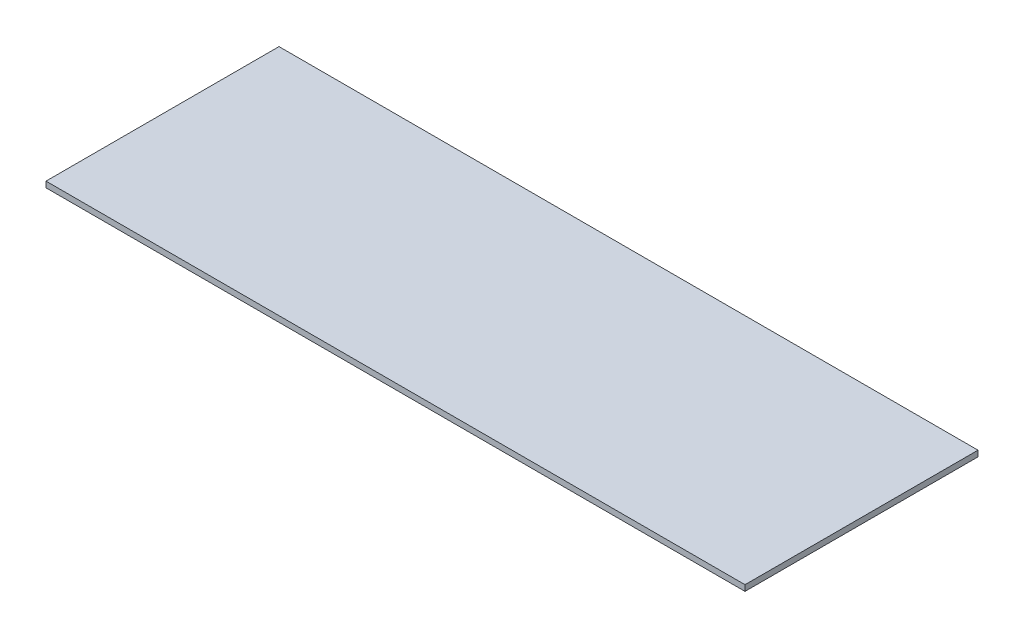
SolidWorks part; units mm, degrees
ref_plane "Front Plane" through (0, 0, 0) normal (0, 0, 1) x (1, 0, 0)
ref_plane "Top Plane" through (0, 0, 0) normal (0, 1, 0) x (1, 0, 0)
ref_plane "Right Plane" through (0, 0, 0) normal (1, 0, 0) x (0, 0, -1)
sketch "Sketch1" plane through (0, 0, 0) normal (0, 1, 0) x (1, 0, 0)
  line L1 (-73.2022, 369.585) -> (1126.7978, 369.585)
  line L2 (-73.2022, 369.585) -> (-73.2022, -30.415)
  line L3 (-73.2022, -30.415) -> (1126.7978, -30.415)
  line L4 (1126.7978, 369.585) -> (1126.7978, -30.415)
extrude "Boss-Extrude1" add sketch "Sketch1" along normal blind 10 contours L2 L3 L4 L1
